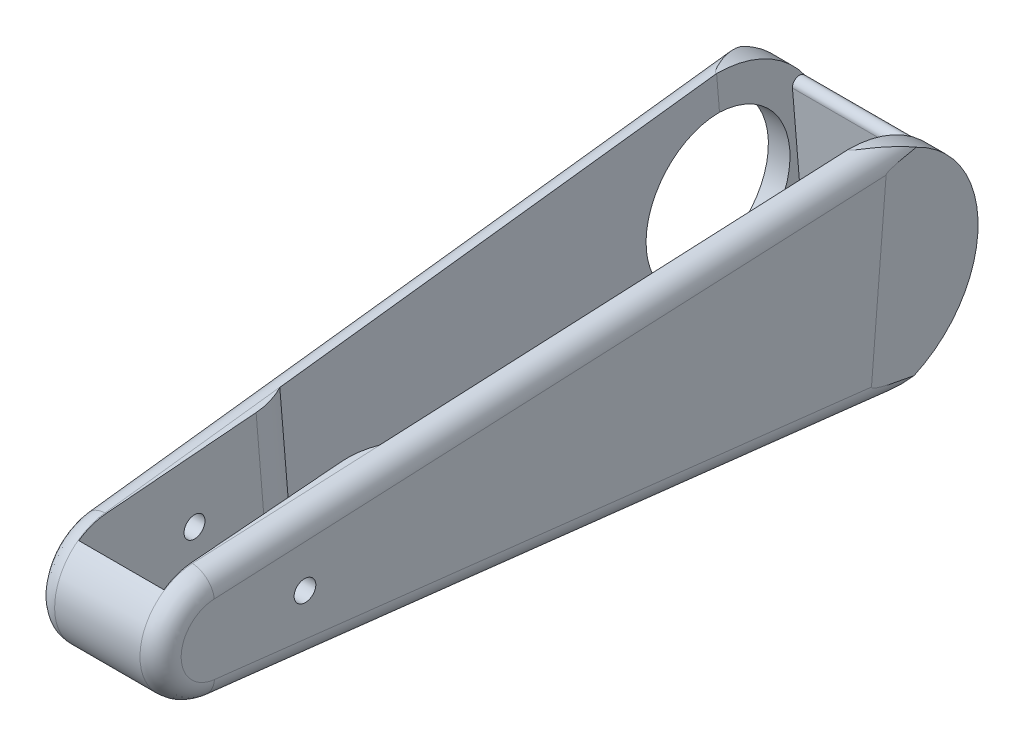
SolidWorks part; units mm, degrees
material "PLA"
ref_plane "Front Plane" through (0, 0, 0) normal (1, 0, 0) x (0, 1, 0)
ref_plane "Top Plane" through (0, 0, 0) normal (0, 0, 1) x (0, 1, 0)
ref_plane "Right Plane" through (0, 0, 0) normal (0, 1, 0) x (-1, 0, 0)
sketch "Sketch1" plane through (0, 0, 0) normal (1, 0, 0) x (0, 0, -1)
  line L0 (0, 15.5) -> (-90.6619, 7.9726)
  line L1 (0, 0) -> (0, 22.3448) construction
  line L2 (-90.6619, -7.9726) -> (0, -15.5)
  circle A0 centre (0, 0) radius 15.5
  arc A1 (-90.6619, 7.9726) -> (-90.6619, -7.9726) centre (-90, 0) ccw
  dimension "D1" = 31
  dimension "D3" = 8
  dimension "D2" = 90
extrude "Boss-Extrude1" add sketch "Sketch1" along normal blind 25 contours L0 A0 L2 | L0 L2 A0 | L0 A1 L2 region at (0, 0, -0.0003) region at (0, 0, 50.0356)
sketch "Sketch4" plane through (0, -15.3939, 1.2781) normal (0, -0.9966, 0.0827) x (1, 0, 0)
  line L0 (0, -1.2825) -> (3.5, 97.6914)
  line L1 (25, 97.6914) -> (0, 97.6914) construction
  line L2 (3.5, 97.6914) -> (21.5, 97.6914)
  line L3 (21.5, 97.6914) -> (25, -1.2825)
  line L4 (25, -1.2825) -> (0, -1.2825)
  line L5 (3.5, 97.6914) -> (0, 97.6914)
  line L6 (25, -1.2825) -> (25, 97.6914)
  line L7 (0, 97.6914) -> (0, -1.2825)
  line L8 (25, 97.6914) -> (21.5, 97.6914)
  line M6 (0, 89.6914) -> (0, -1.2825)
  line M8 (25, -1.2825) -> (25, 89.6914)
  line M9 (25, 89.6914) -> (0, 89.6914)
  dimension "D1" = 18
extrude "Cut-Extrude1" cut sketch "Sketch4" against normal up to next contours L0 M6 M9 | L5 L7 L0 M9 | L6 L8 L3 M9 | L3 M9 M8 region at (1.0724, -10.4817, 60.4413) region at (1.6803, -7.6369, 94.7042) region at (23.9276, -10.4817, 60.4413) region at (23.3197, -7.6369, 94.7042)
sketch "Sketch7" plane through (0, 15.3939, 1.2781) normal (0, 0.9966, 0.0827) x (-1, 0, 0)
  line L0 (-0.0907, -1.2825) -> (-24.9093, -1.2825)
  line L1 (-21.7362, 89.6914) -> (-3.2638, 89.6914)
  line L2 (-18.7344, 89.6914) -> (-21.9075, -1.2825)
  line L3 (-6.2656, 89.6914) -> (-3.0925, -1.2825)
  line L4 (-24.9093, -1.2825) -> (-21.7362, 89.6914) construction
  line L5 (-3.2638, 89.6914) -> (-0.0907, -1.2825) construction
  line L6 (-21.9075, -1.2825) -> (-21.9075, -11.5)
  line L7 (-21.9075, -11.5) -> (-3.0925, -11.5)
  line L8 (-3.0925, -11.5) -> (-3.0925, -1.2825)
  line L9 (-25, -15.5) -> (0, -15.5) construction
  line L10 (-18.7344, 89.6914) -> (-18.5949, 93.6914)
  line L11 (-18.5949, 93.6914) -> (-6.4051, 93.6914)
  line L12 (-6.4051, 93.6914) -> (-6.2656, 89.6914)
  line L13 (-3.4961, 97.6914) -> (-21.5039, 97.6914) construction
  line L14 (-18.5949, 93.6914) -> (-18.5949, 63.6914)
  line L15 (-18.5949, 63.6914) -> (-6.4051, 63.6914)
  line L16 (-6.4051, 63.6914) -> (-6.4051, 93.6914)
  line L17 (-6.4051, 63.6914) -> (-5.3587, 63.6914)
  line L18 (-18.5949, 63.6914) -> (-19.6413, 63.6914)
  line M11 (-3.2638, 89.6914) -> (-21.7362, 89.6914)
  dimension "D1" = 3
  dimension "D2" = 3
  dimension "D3" = 4
  dimension "D4" = 4
  dimension "D5" = 30
extrude "Cut-Extrude2" cut sketch "Sketch7" against normal up to next contours L3 L1 L2 L0 | L7 L8 L0 L6 | L15 L16 L14 M11 | L16 L11 L14 M11 region at (12.5, 15.9227, -5.0912) region at (12.5, 12.9346, 30.8977) region at (12.5, 9.0482, 77.7065) region at (12.5, 7.8071, 92.6551)
sketch "Sketch8" plane through (0, 0, 0) normal (-1, 0, 0) x (0, -1, 0)
  circle A0 centre (0, 0) radius 10.5
  dimension "D1" = 21
extrude "Cut-Extrude3" cut sketch "Sketch8" against normal up to next
fillet "Fillet1" radius 10 2 edges at (6.4051, -0.0703, 63.9047) (18.5949, -0.0703, 63.9047)
fillet "Fillet2" radius 3 6 edges at (23.3915, -11.7363, 45.331) (21.501, 0, 98) (1.6085, -11.7363, 45.331) (3.499, 0, 98) (23.3228, 11.7363, 45.331) (1.6772, 11.7363, 45.331)
fillet "Fillet3" radius 1 2 edges at (12.5, -9.4051, -12.3205) (12.5, 11.3082, -10.6007)
sketch "Sketch9" plane through (0, 0, 0) normal (1, 0, 0) x (0, 1, 0)
  line L0 (0, 98) -> (0, 78) construction
  line L1 (0, 0) -> (0, 82.8492) construction
  circle A0 centre (0, 78) radius 1.5
  arc A1 (7.9726, 90.6619) -> (-7.9726, 90.6619) centre (0, 90) ccw construction
  dimension "D1" = 3
  dimension "D2" = 20
extrude "Cut-Extrude4" cut sketch "Sketch9" along normal through all both and the other way through all
